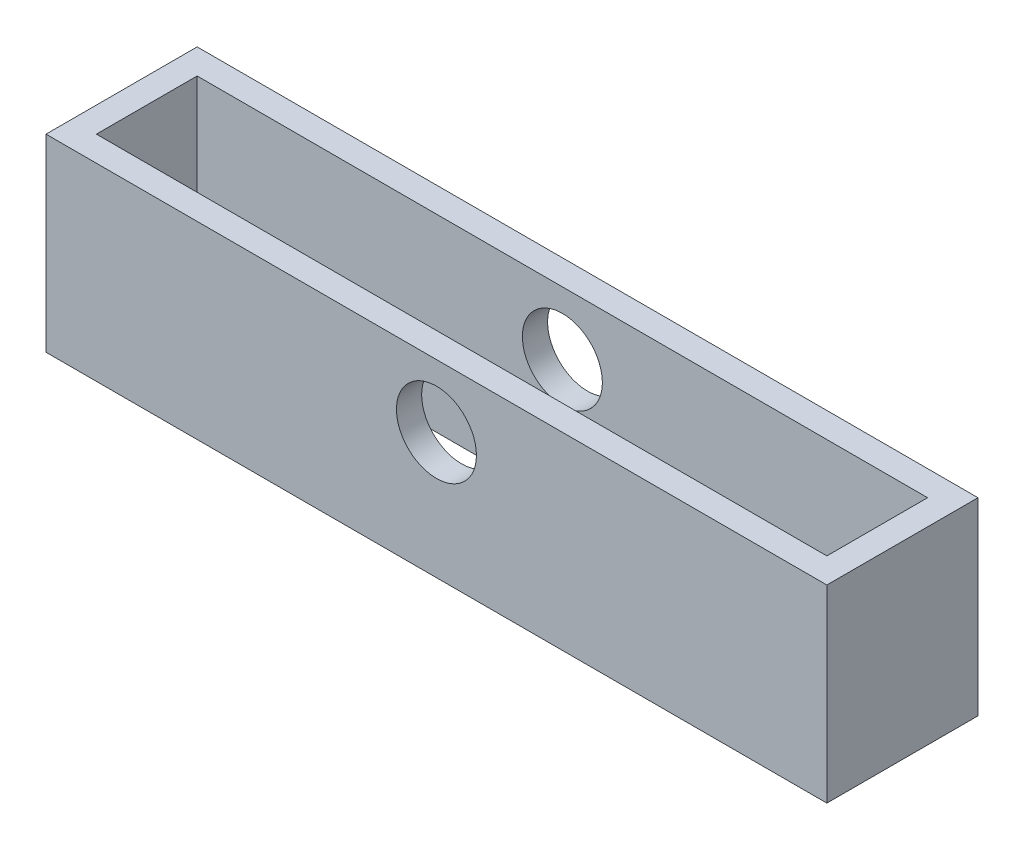
SolidWorks part; units mm, degrees
ref_plane "Front" through (0, 0, 0) normal (0, 0, 1) x (1, 0, 0)
ref_plane "Top" through (0, 0, 0) normal (0, 1, 0) x (1, 0, 0)
ref_plane "Right" through (0, 0, 0) normal (1, 0, 0) x (0, 0, -1)
sketch "Esquisse1" plane through (0, 0, 0) normal (0, 1, 0) x (1, 0, 0)
  line L1 (-31, 6) -> (31, 6)
  line L2 (-31, 6) -> (-31, -6)
  line L3 (-31, -6) -> (31, -6)
  line L4 (31, 6) -> (31, -6)
  line L5 (-31, 6) -> (31, -6) construction
  line L6 (-31, -6) -> (31, 6) construction
  line L7 (-29, 4) -> (29, 4)
  line L8 (-29, 4) -> (-29, -4)
  line L9 (-29, -4) -> (29, -4)
  line L10 (29, 4) -> (29, -4)
  line L11 (-29, 4) -> (29, -4) construction
  line L12 (-29, -4) -> (29, 4) construction
  point P0 (0, 0)
  point P6 (0, 0)
  point P11 (0, 0)
  dimension "D1" = 8
  dimension "D2" = 12
  dimension "D3" = 62
  dimension "D4" = 58
extrude "Boss.-Extru.1" add sketch "Esquisse1" along normal blind 15
sketch "Esquisse2" plane through (0, 0, 6) normal (0, 0, 1) x (1, 0, 0)
  line L0 (-31, 15) -> (31, 15) construction
  line L1 (31, 15) -> (31, 0) construction
  circle A0 centre (0, 10) radius 3.175
  dimension "D1" = 6.35
  dimension "D2" = 5
  dimension "D3" = 31
extrude "Enlèv. mat.-Extru.1" cut sketch "Esquisse2" against normal through all
